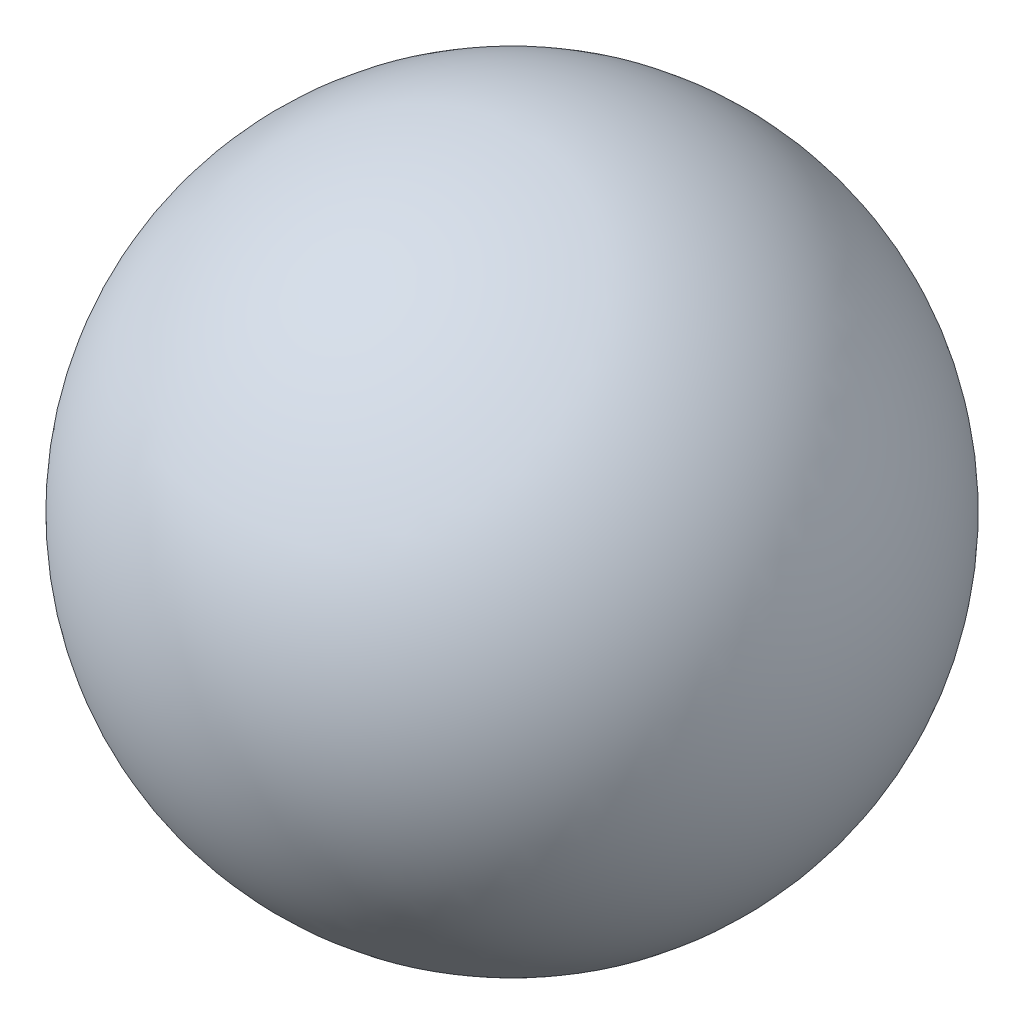
SolidWorks part; units mm, degrees
ref_plane "Front Plane" through (0, 0, 0) normal (0, 0, 1) x (1, 0, 0)
ref_plane "Top Plane" through (0, 0, 0) normal (0, 1, 0) x (1, 0, 0)
ref_plane "Right Plane" through (0, 0, 0) normal (1, 0, 0) x (0, 0, -1)
sketch "Sketch1" plane through (0, 0, 0) normal (1, 0, 0) x (0, 0, -1)
  line L0 (0, -43.5884) -> (0, 46.7278) construction
  circle A0 centre (0, 0) radius 38.1
  dimension "D1" = 76.2
revolve "Revolve3" add sketch "Sketch1" angle 360 about L0 region at (0, 0, -16.1701)
